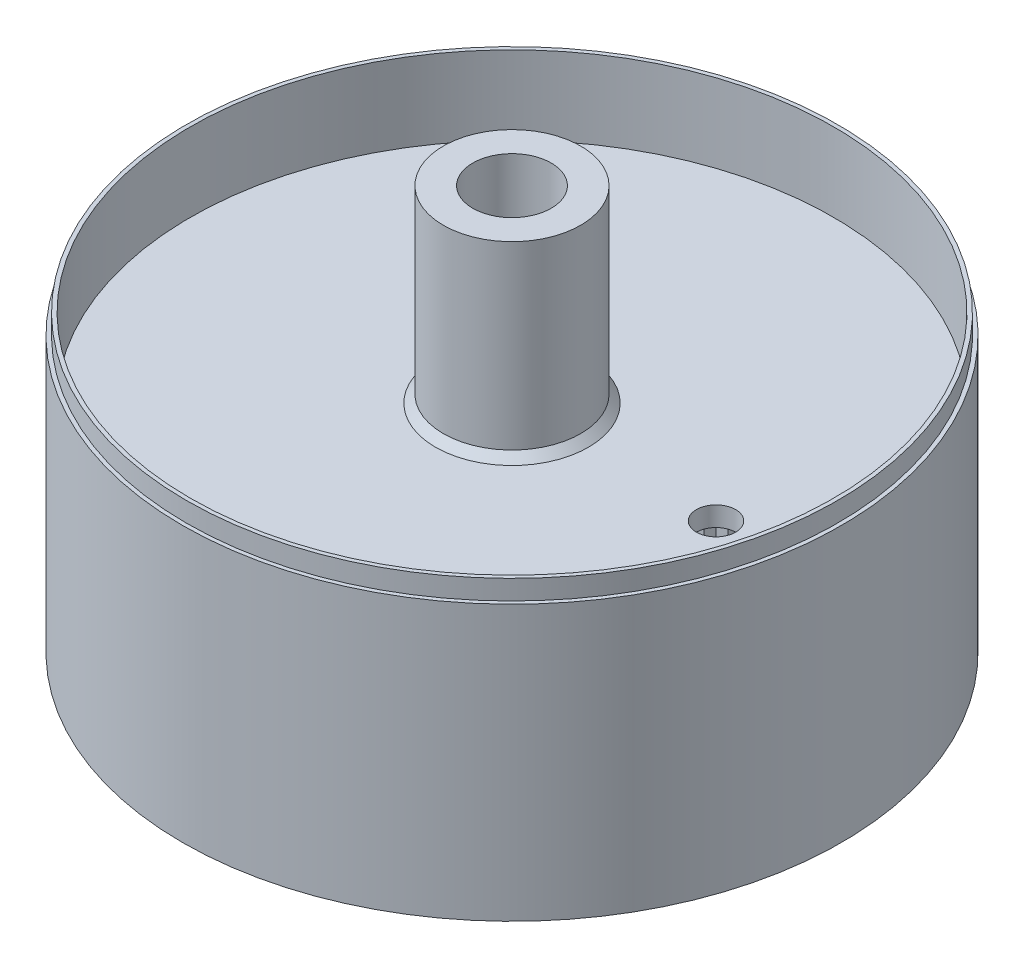
SolidWorks part; units mm, degrees
ref_plane "Alzado" through (0, 0, 0) normal (0, 0, 1) x (1, 0, 0)
ref_plane "Planta" through (0, 0, 0) normal (0, 1, 0) x (1, 0, 0)
ref_plane "Vista lateral" through (0, 0, 0) normal (1, 0, 0) x (0, 0, -1)
sketch "Croquis1" plane through (0, 0, 0) normal (0, 1, 0) x (1, 0, 0)
  circle A0 centre (0, 0) radius 84
  dimension "D1" = 168
extrude "Saliente-Extruir1" add sketch "Croquis1" against normal blind 5 contours A0
sketch "Croquis15" plane through (0, -5, 0) normal (0, -1, 0) x (1, 0, 0)
  circle A0 centre (0, 0) radius 20
  dimension "D1" = 40
sketch "Croquis5" plane through (0, 0, 0) normal (0, 1, 0) x (1, 0, 0)
  circle A0 centre (0, 0) radius 82
  circle A2 centre (0, 0) radius 84
  dimension "D1" = 164
extrude "Saliente-Extruir2" add sketch "Croquis5" along normal blind 20 contours A0 | A2
sketch "Croquis20" plane through (0, 0, 0) normal (0, 1, 0) x (1, 0, 0)
  circle A0 centre (0, 0) radius 17.5
  dimension "D1" = 35
extrude "Eje Engrane Central" add sketch "Croquis20" along normal blind 48
sketch "Croquis21" plane through (0, 0, 0) normal (0, 1, 0) x (1, 0, 0)
  circle A0 centre (52, 0) radius 5
  dimension "D1" = 10
  dimension "D2" = 52
  dimension "D3" = 0
ref_axis "Eje2" through (0, 63.7553, 0) along (0, -1, 0)
extrude "Cortar-Extruir2" cut sketch "Croquis21" against normal blind 15
ref_axis "Eje3" through (52, -35.696, 0) along (0, 1, 0)
ref_plane "Plano4" through (0, 0, 0) normal (0, 0, 1) x (1, 0, 0)
ref_axis "Eje4" through (-92.4, 0, 0) along (1, 0, 0)
sketch "Croquis23" plane through (0, 20, 0) normal (0, 1, 0) x (1, 0, 0)
  circle A0 centre (0, 0) radius 84
  circle A1 centre (0, 0) radius 83
  dimension "D1" = 166
  dimension "D2" = 168
extrude "Cortar-Extruir3" cut sketch "Croquis23" against normal blind 5
ref_point "Punto1"
sketch "Croquis30" plane through (0, 48, 0) normal (0, 1, 0) x (1, 0, 0)
  circle A0 centre (0, 0) radius 10
  dimension "D1" = 20
extrude "Cortar-Extruir8" cut sketch "Croquis30" against normal blind 73
chamfer "Chaflán5" distance 2 angle 45 1 edges at (0, 0, 17.5)
sketch "Croquis33" plane through (0, -5, 0) normal (0, -1, 0) x (1, 0, 0)
  circle A0 centre (0, 0) radius 84
  circle A1 centre (0, 0) radius 81
  dimension "D1" = 168
  dimension "D2" = 162
extrude "Saliente-Extruir7" add sketch "Croquis33" along normal blind 50
sketch "Croquis34" plane through (0, -5, 0) normal (0, -1, 0) x (1, 0, 0)
  line L2 (29.5, 17.5) -> (31.5, 17.5)
  line L3 (74.5, -22.5) -> (69.5, -22.5)
  line L4 (74.5, -22.5) -> (74.5, -17.5)
  line L5 (74.5, 22.5) -> (69.5, 22.5)
  line L6 (29.5, -22.5) -> (29.5, -17.5)
  line L7 (74.5, -22.5) -> (72.5, -20.5) construction
  line L8 (74.5, 22.5) -> (72.5, 20.5) construction
  line L9 (72.5, -20.5) -> (69.5, -20.5)
  line L10 (72.5, -20.5) -> (72.5, -17.5)
  line L11 (72.5, 20.5) -> (69.5, 20.5)
  line L12 (31.5, -20.5) -> (31.5, -17.5)
  line L15 (34.5, 20.5) -> (34.5, 22.5)
  line L16 (69.5, 22.5) -> (69.5, 20.5)
  line L17 (72.5, 17.5) -> (74.5, 17.5)
  line L18 (72.5, -17.5) -> (74.5, -17.5)
  line L19 (69.5, -20.5) -> (69.5, -22.5)
  line L20 (34.5, -20.5) -> (34.5, -22.5)
  line L21 (31.5, -17.5) -> (29.5, -17.5)
  line L22 (34.5, 22.5) -> (29.5, 22.5)
  line L23 (34.5, 20.5) -> (31.5, 20.5)
  line L24 (72.5, 17.5) -> (72.5, 20.5)
  line L25 (74.5, 17.5) -> (74.5, 22.5)
  line L28 (31.5, -20.5) -> (29.5, -22.5) construction
  line L30 (31.5, 20.5) -> (29.5, 22.5) construction
  line L31 (31.5, 17.5) -> (31.5, 20.5)
  line L32 (29.5, 17.5) -> (29.5, 22.5)
  line L33 (34.5, -20.5) -> (31.5, -20.5)
  line L34 (34.5, -22.5) -> (29.5, -22.5)
  circle A1 centre (52, 0) radius 5 construction
  dimension "D2" = 3
  dimension "D3" = 2
  dimension "D4" = 35
  dimension "D5" = 35
  dimension "D6" = 35
  dimension "D7" = 5
  dimension "D8" = 5
  dimension "D9" = 5
  dimension "D10" = 5
  dimension "D11" = 35
  dimension "D12" = 5
  dimension "D13" = 3
extrude "Saliente-Extruir8" add sketch "Croquis34" along normal blind 32
sketch "Croquis35" plane through (0, -55, 0) normal (0, -1, 0) x (1, 0, 0)
  circle A0 centre (0, 0) radius 81
  circle A1 centre (0, 0) radius 83
  dimension "D1" = 2
  dimension "D2" = 162
extrude "Cortar-Extruir9" cut sketch "Croquis35" against normal blind 10
thread "Rosca1" pitch 1.5 method extrude profile "Perfil de rosca1" start angle 0, offset 0, length 10, pitch 1.5, diameter 166
ref_plane "Plano5" through (83, -55, 0) normal (0, 0, 1) x (1, 0, 0)
sketch "Perfil de rosca1" plane through (83, -55, 0) normal (0, 0, 1) x (1, 0, 0)
  line L0 (0, 0) -> (0, 1.5) construction
  line L11 (0, 0) -> (0, 1.3125)
  line L12 (0, 1.3125) -> (-0.8119, 0.8437)
  line L13 (-0.8119, 0.8437) -> (-0.8119, 0.4687)
  line L15 (-0.8119, 0.4687) -> (0, 0)
  line L17 (-0.8119, 0.6562) -> (0, 0.6562) construction
  point P2 (0, 0)
  dimension "Pitch" = 1.5
  dimension "Profile_Angle" = 60
  dimension "Profile_Land" = 0.375
  dimension "Profile_Height" = 0.8119
sketch "Croquis37" plane through (0, 0, 0) normal (0, 1, 0) x (1, 0, 0)
  line L0 (0, 0) -> (-84, 0) construction
  line L6 (-74, 32.5) -> (-20, 32.5) construction
  line L7 (-74, 32.5) -> (-74, -32.5) construction
  line L8 (-74, -32.5) -> (-71, -32.5) construction
  line L9 (-20, 32.5) -> (-20, -32.5) construction
  line L10 (-71, -32.5) -> (-68.1716, -35.3284) construction
  line L11 (-68.1716, -35.3284) -> (-34.8284, -35.3284) construction
  line L12 (-34.8284, -35.3284) -> (-32, -32.5) construction
  line L13 (-32, -32.5) -> (-20, -32.5) construction
  circle A0 centre (-57, -33.0284) radius 1.5
  circle A1 centre (-71.7, 17.5) radius 1.5
  circle A2 centre (-22.3, 18.5) radius 1.5
  circle A3 centre (-27, -33.0284) radius 1.5
  dimension "D11" = 3
  dimension "D15" = 3
  dimension "D19" = 3
  dimension "D22" = 3
  dimension "D1" = 54
  dimension "D2" = 65
  dimension "D3" = 10
  dimension "D4" = 32.5
  dimension "D5" = 3
  dimension "D6" = 4
  dimension "D7" = 12
  dimension "D8" = 4
  dimension "D9" = 45
  dimension "D10" = 45
  dimension "D12" = 15
  dimension "D13" = 2.3
  dimension "D14" = 14
  dimension "D16" = 84
  dimension "D17" = 2.3
  dimension "D18" = 17
  dimension "D20" = 2.3
  dimension "D21" = 7
  dimension "D23" = 2.3
extrude "Saliente-Extruir9" add sketch "Croquis37" against normal blind 10
